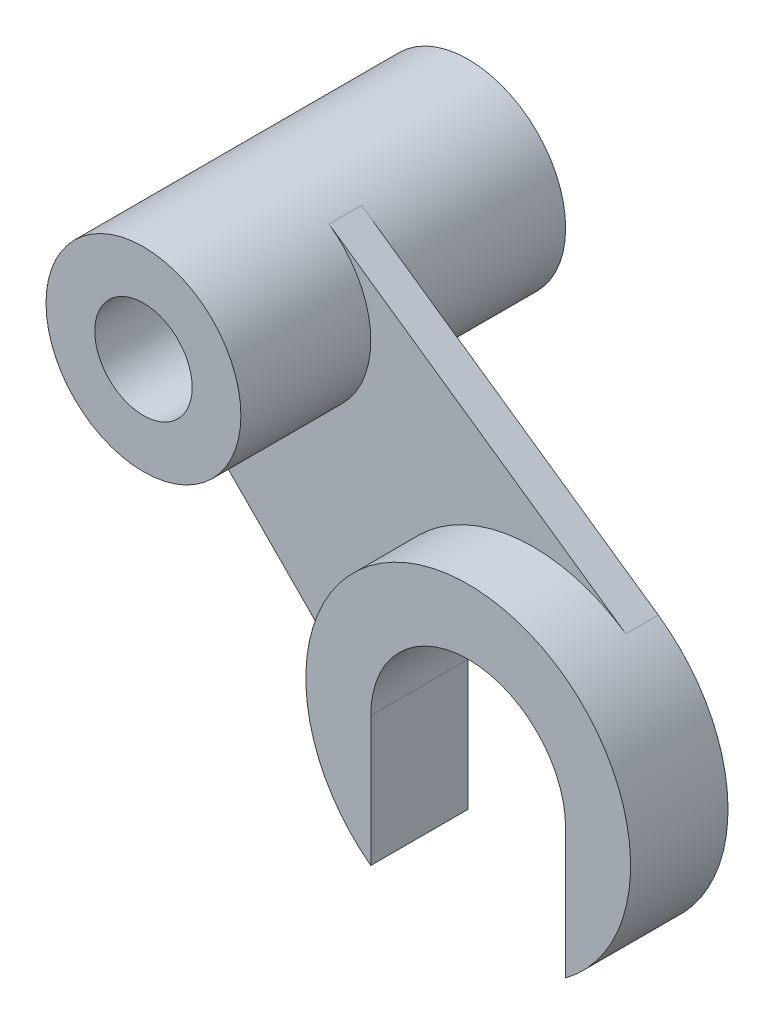
SolidWorks part; units mm, degrees
ref_plane "Front Plane" through (0, 0, 0) normal (0, 0, 1) x (1, 0, 0)
ref_plane "Top Plane" through (0, 0, 0) normal (0, 1, 0) x (1, 0, 0)
ref_plane "Right Plane" through (0, 0, 0) normal (1, 0, 0) x (0, 0, -1)
sketch "Sketch1" plane through (0, 0, 0) normal (0, 0, 1) x (1, 0, 0)
  line L0 (80, -40) -> (80, -80)
  line L1 (140, -40) -> (140, -80)
  line L2 (47.1291, 64.6291) -> (138.5485, 1.0485)
  line L3 (0, 40) -> (0, 0)
  line L4 (0, 0) -> (74.4774, -75.1872)
  circle A0 centre (30, 40) radius 30
  circle A1 centre (30, 40) radius 15
  arc A2 (140, -40) -> (80, -40) centre (110, -40) ccw
  arc A3 (140, -80) -> (80, -80) centre (110, -40) ccw
  point P12 (47.3444, 74.4435)
  point P14 (0, 0)
  dimension "D1" = 30
  dimension "D2" = 60
  dimension "D5" = 50
  dimension "D6" = 30
  dimension "D3" = 80
  dimension "D4" = 80
  dimension "D7" = 40
extrude "Boss-Extrude1" add sketch "Sketch1" along normal blind 100 contours A0 A1 region at (16.4983, 65.8363, 0)
extrude "Boss-Extrude2" add sketch "Sketch1<3>" along normal blind 10 from offset 50 contours A3 L2 A0 L3 L4 region at (54.8601, 1.8258, 0)
sketch "Sketch1<3>" plane through (0, 0, 0) normal (0, 0, 1) x (1, 0, 0) same geometry as "Sketch1"
extrude "Boss-Extrude3" add sketch "Sketch1<4>" along normal blind 30 from offset 50 contours A3 L0 A2 L1 region at (78.6546, -60, 0)
sketch "Sketch1<4>" plane through (0, 0, 0) normal (0, 0, 1) x (1, 0, 0) same geometry as "Sketch1"
